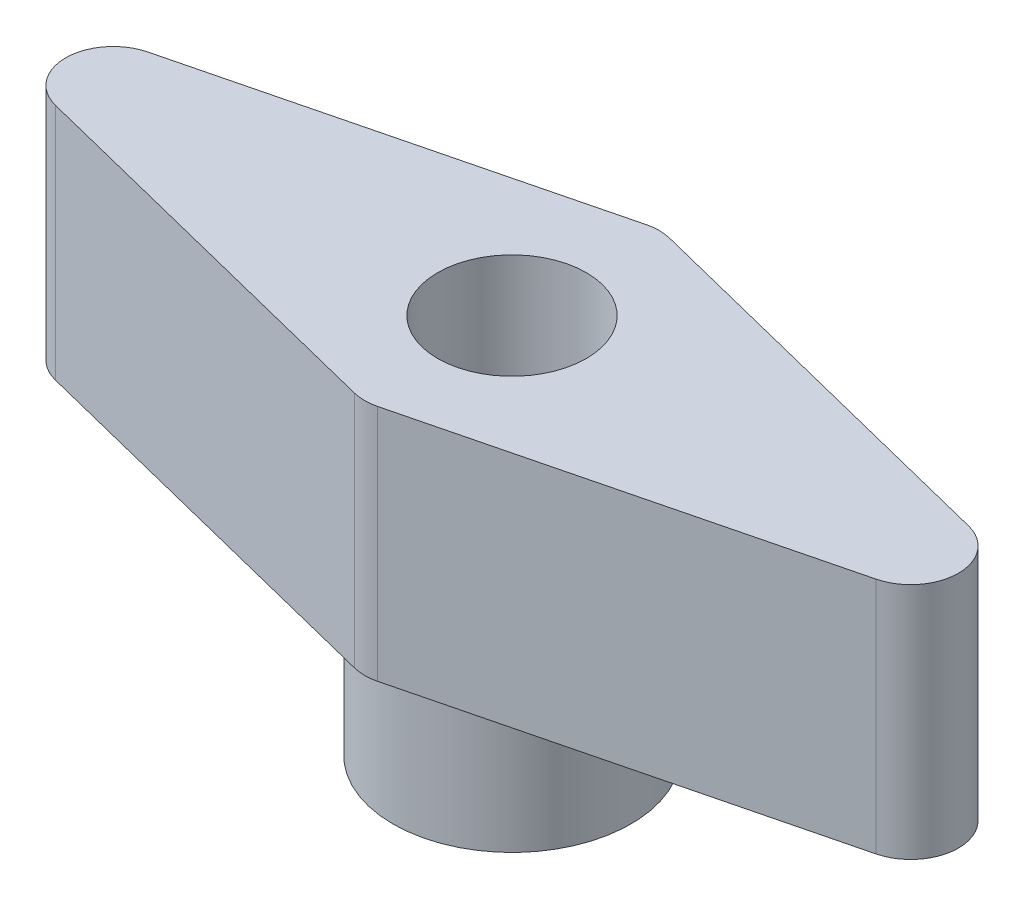
SolidWorks part; units mm, degrees
material "NEOPRENE"
ref_plane "Front Plane" through (0, 0, 0) normal (0, 0, 1) x (1, 0, 0)
ref_plane "Top Plane" through (0, 0, 0) normal (0, 1, 0) x (1, 0, 0)
ref_plane "Right Plane" through (0, 0, 0) normal (1, 0, 0) x (0, 0, -1)
sketch "Sketch1" plane through (0, 0, 0) normal (0, 1, 0) x (1, 0, 0)
  line L0 (-21.8934, -2.4642) -> (-0.616, -7.7835)
  line L1 (-21.8934, 2.4642) -> (-0.616, 7.7835)
  line L2 (0.616, -7.7835) -> (21.8934, -2.4642)
  line L3 (0.616, 7.7835) -> (21.8934, 2.4642)
  line L4 (0, 7.9375) -> (0, -7.9375) construction
  line L5 (-31.75, 0) -> (31.75, 0) construction
  arc A0 (21.8934, -2.4642) -> (21.8934, 2.4642) centre (21.2773, 0) ccw
  arc A1 (-0.616, 7.7835) -> (0.616, 7.7835) centre (0, 5.3193) cw
  arc A2 (-0.616, -7.7835) -> (0.616, -7.7835) centre (0, -5.3193) ccw
  arc A3 (-21.8934, 2.4642) -> (-21.8934, -2.4642) centre (-21.2773, 0) ccw
  dimension "D3" = 2.54
  dimension "D1" = 63.5
  dimension "D2" = 15.875
extrude "Boss-Extrude1" add sketch "Sketch1" against normal blind 12.7
shell "Shell1" thickness 2.54 removed face at (0, -12.7, 0)
fillet "Fillet1" radius 0.508 4 edges at (21.2773, -7.62, 0) (0, -7.62, -5.3193) (0, -7.62, 5.3193) (-21.2773, -7.62, 0)
sketch "Sketch2" plane through (0, 0, 0) normal (0, 1, 0) x (1, 0, 0)
  circle A0 centre (0, 0) radius 6.35
  circle A1 centre (0, 0) radius 3.9688
  dimension "D1" = 7.9375
  dimension "D2" = 12.7
extrude "Boss-Extrude2" add sketch "Sketch2" against normal blind 20.32
sketch "Sketch3" plane through (0, -2.54, 0) normal (0, -1, 0) x (1, 0, 0)
  circle A1 centre (0, 0) radius 3.9688
  circle A2 centre (0, 0) radius 3.9688
  dimension "D1" = 0
extrude "Cut-Extrude1" cut sketch "Sketch3" against normal through all
